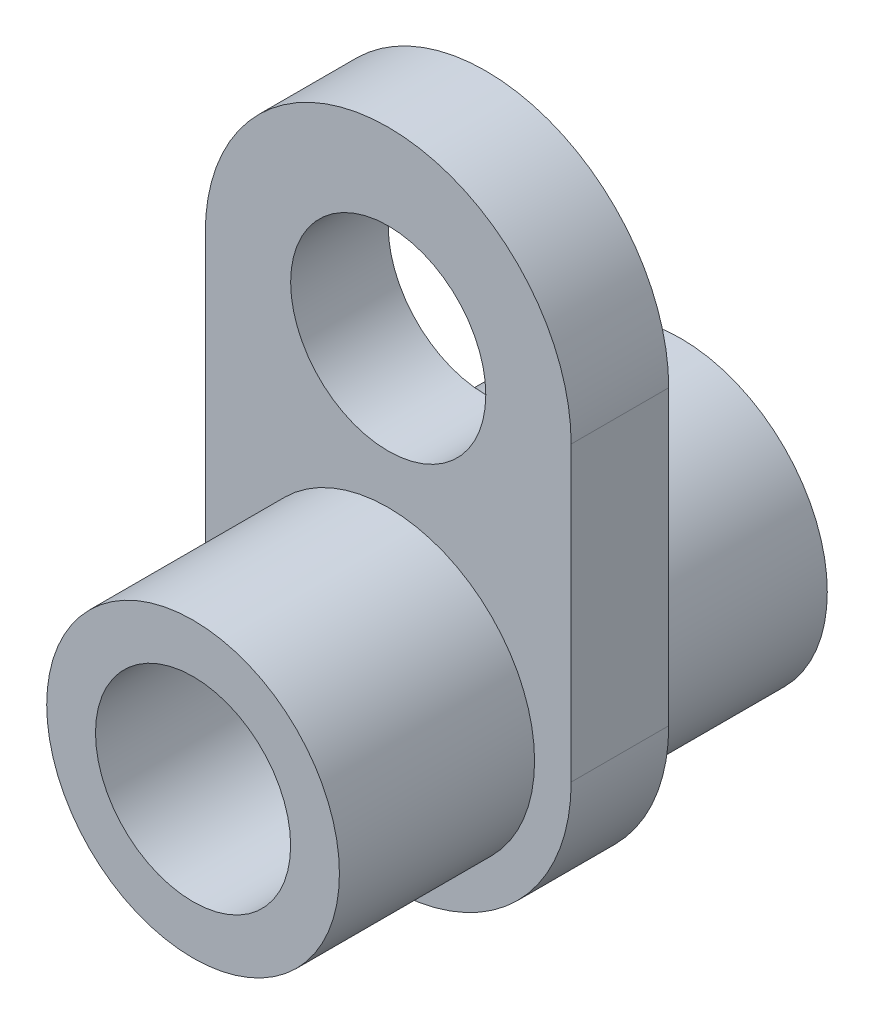
SolidWorks part; units mm, degrees
ref_plane "Alzado" through (0, 0, 0) normal (0, 0, 1) x (1, 0, 0)
ref_plane "Planta" through (0, 0, 0) normal (0, 1, 0) x (1, 0, 0)
ref_plane "Vista lateral" through (0, 0, 0) normal (1, 0, 0) x (0, 0, -1)
sketch "Croquis1" plane through (0, 0, 0) normal (0, 0, 1) x (1, 0, 0)
  circle A0 centre (0, -6) radius 4
sketch_block_instance "binario 2-2"
sketch_block "binario 2" parameters "D2"=8, "D1"=12
sketch "Croquis2" plane through (0, 0, 0) normal (0, 0, 1) x (1, 0, 0)
  line L0 (0, 6) -> (0, -6) construction
  line L1 (7.5, 6) -> (7.5, -6)
  line L2 (-7.5, 6) -> (-7.5, -6)
  circle A0 centre (0, -6) radius 4 construction
  circle A1 centre (0, 6) radius 4 construction
  circle A2 centre (0, -6) radius 4
  circle A3 centre (0, 6) radius 4
  arc A4 (7.5, 6) -> (-7.5, 6) centre (0, 6) ccw
  arc A5 (-7.5, -6) -> (7.5, -6) centre (0, -6) ccw
  circle A6 centre (0, -6) radius 6
  point P6 (0, 0)
  dimension "D1" = 7.5
  dimension "D2" = 2
extrude "Saliente-Extruir1" add sketch "Croquis2" along normal blind 2 and the other way blind 2 contours L2 A5 L1 A4 A3 A6 | A6 A2 region at (0, 1.9498, 0) region at (-5.8303, -6, 0)
extrude "Saliente-Extruir2" add sketch "Croquis2<3>" along normal blind 10 and the other way blind 10 contours A6 A2 region at (-5.8303, -6, 0)
sketch "Croquis2<3>" plane through (0, 0, 0) normal (0, 0, 1) x (1, 0, 0) same geometry as "Croquis2"
